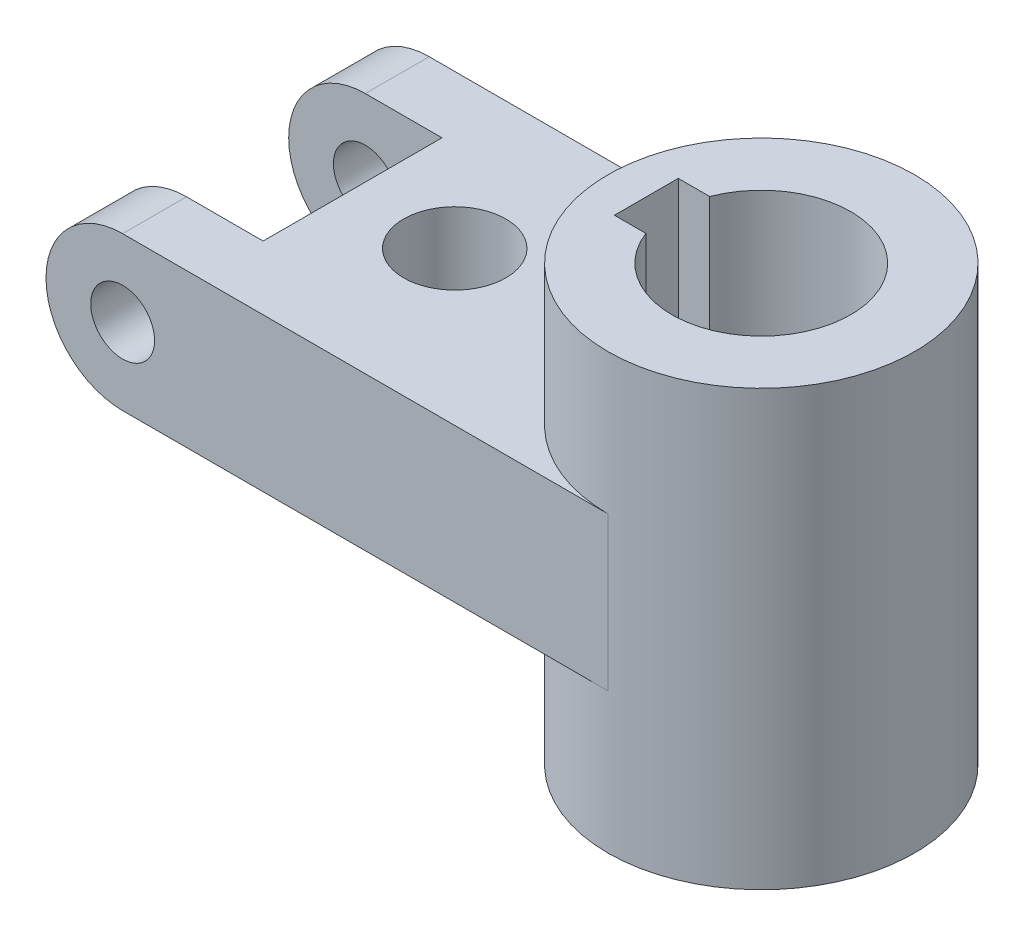
SolidWorks part; units mm, degrees
ref_plane "Front Plane" through (0, 0, 0) normal (0, 0, 1) x (1, 0, 0)
ref_plane "Top Plane" through (0, 0, 0) normal (0, 1, 0) x (1, 0, 0)
ref_plane "Right Plane" through (0, 0, 0) normal (1, 0, 0) x (0, 0, -1)
sketch "Sketch1" plane through (0, 0, 0) normal (0, 1, 0) x (1, 0, 0)
  line L0 (-22, -12) -> (22, -12)
  line L1 (-22, -12) -> (-22, -7)
  line L2 (22, -12) -> (22, 12)
  line L3 (-22, 12) -> (22, 12)
  line L4 (-22, -12) -> (22, 12) construction
  line L5 (22, -12) -> (-22, 12) construction
  line L6 (29, 0) -> (-22, 0) construction
  line L8 (13, 2.5) -> (15.4617, 2.5)
  line L9 (13, 2.5) -> (13, -2.5)
  line L10 (13, -2.5) -> (15.4617, -2.5)
  line L11 (-22, 7) -> (-22, 12)
  line L12 (-22, 7) -> (-10, 7)
  line L13 (-22, -7) -> (-10, -7)
  line L14 (-10, 7) -> (-10, -7)
  circle A0 centre (22, 0) radius 12
  circle A2 centre (-2, 0) radius 4
  arc A3 (15.4617, -2.5) -> (15.4617, 2.5) centre (22, 0) ccw
  point P1 (0, 0)
  point P10 (0, 0)
  point P14 (-10, 0)
  dimension "D1" = 24
  dimension "D2" = 14
  dimension "D3" = 8
  dimension "D4" = 44
  dimension "D5" = 24
  dimension "D6" = 14
  dimension "D7" = 8
  dimension "D8" = 5
  dimension "D9" = 16
extrude "Boss-Extrude1" add sketch "Sketch1" along normal blind 17 and the other way blind 17 contours A3 L2 A0 | A3 L2 A0 L10 L9 L8 region at (10.2683, 0, 0) region at (22.2683, 0, 9.5)
extrude "Boss-Extrude2" add sketch "Sketch1<3>" along normal blind 6 and the other way blind 6 contours A0 L3 L11 L12 L14 L13 L1 L0 A2 region at (-21.4988, 0, 9.5)
sketch "Sketch1<3>" plane through (0, 0, 0) normal (0, 1, 0) x (1, 0, 0) same geometry as "Sketch1"
sketch "Sketch2" plane through (0, 0, 12) normal (0, 0, 1) x (1, 0, 0)
  line L0 (-22, -6) -> (22, -6) construction
  line L1 (-22, 6) -> (-16, 6)
  line L2 (-22, 6) -> (-22, -6)
  line L3 (-22, -6) -> (-16, -6)
  line L4 (-16, 6) -> (-16, -6)
  arc A0 (-16, 6) -> (-16, -6) centre (-16, 0) ccw
  circle A1 centre (-16, 0) radius 2.5
  line M2 (22, 6) -> (-22, 6)
  line M3 (-22, 6) -> (-22, -6)
  line M4 (-22, -6) -> (22, -6)
  dimension "D2" = 5
  dimension "D1" = 6
extrude "Cut-Extrude1" cut sketch "Sketch2" against normal through all contours A0 M2 M3 | A0 L2 M4 | A1 region at (-20.6598, 4.6598, 12) region at (-20.6598, -4.6598, 12)
